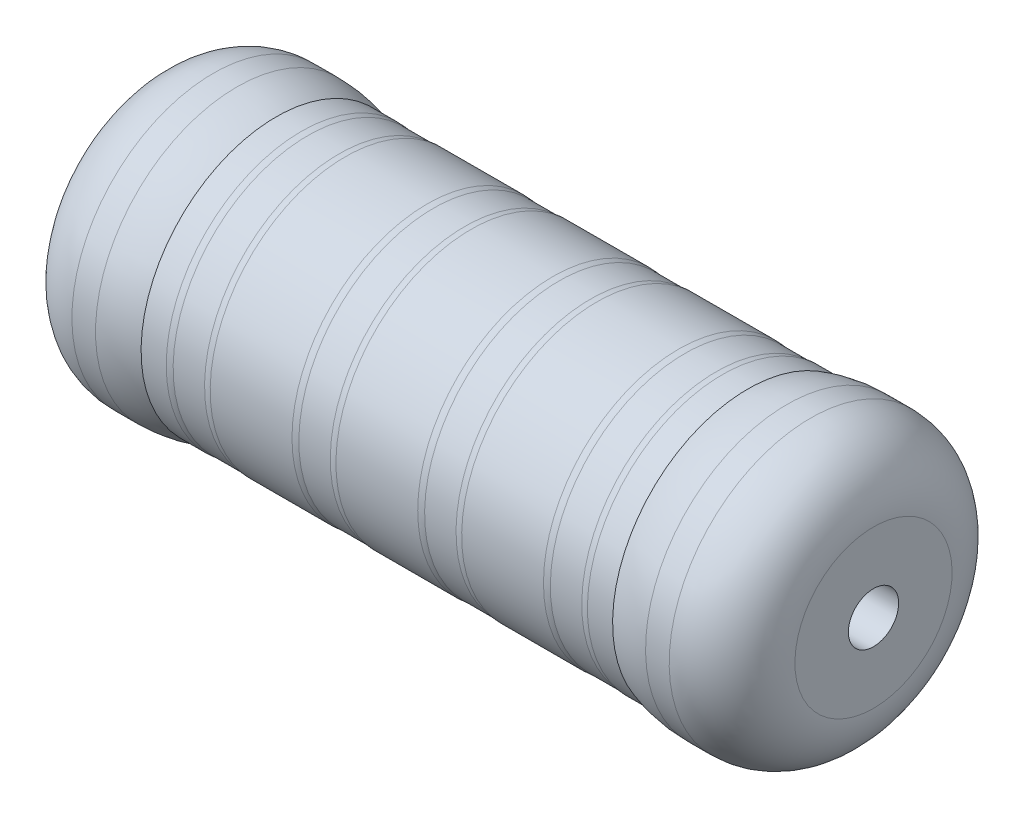
SolidWorks part; units mm, degrees
ref_plane "Front Plane" through (0, 0, 0) normal (0, 0, 1) x (1, 0, 0)
ref_plane "Top Plane" through (0, 0, 0) normal (0, 1, 0) x (1, 0, 0)
ref_plane "Right Plane" through (0, 0, 0) normal (1, 0, 0) x (0, 0, -1)
sketch "Sketch2" plane through (0, 0, 0) normal (0, 0, 1) x (1, 0, 0)
  line L0 (-6.5581, 0) -> (4.9419, 0) construction
  line L1 (-6.5581, 0) -> (-6.5581, 2.25)
  line L2 (4.9419, 0) -> (4.9419, 2.25)
  line L3 (-6.5581, 2.25) -> (-4.5581, 2.25)
  line L4 (-4.5581, 2.25) -> (-4.5581, 2.15)
  line L5 (1.4421, 2.15) -> (2.9419, 2.15)
  line L6 (2.9419, 2.15) -> (2.9419, 2.25)
  line L7 (2.9419, 2.25) -> (4.9419, 2.25)
  line L8 (-4.0581, 2.15) -> (-4.0581, 2.14)
  line L9 (-4.0581, 2.14) -> (-3.5581, 2.14)
  line L10 (-3.5581, 2.14) -> (-3.5581, 2.15)
  line L11 (-3.5581, 2.15) -> (-2.0581, 2.15)
  line L12 (-2.0581, 2.15) -> (-2.0581, 2.14)
  line L13 (-2.0581, 2.14) -> (-1.5581, 2.14)
  line L14 (-1.5581, 2.14) -> (-1.5581, 2.15)
  line L15 (-1.5581, 2.15) -> (-0.0581, 2.15)
  line L16 (-0.0581, 2.15) -> (-0.0581, 2.14)
  line L17 (-0.0581, 2.14) -> (0.4419, 2.14)
  line L18 (0.4419, 2.14) -> (0.4419, 2.15)
  line L19 (0.4419, 2.15) -> (1.9419, 2.15)
  line L20 (1.9419, 2.15) -> (1.9419, 2.14)
  line L21 (1.9419, 2.14) -> (2.4419, 2.14)
  line L22 (2.4419, 2.14) -> (2.4419, 2.15)
  line L23 (-4.5581, 2.15) -> (-4.0581, 2.15)
  line L24 (2.4419, 2.15) -> (2.9419, 2.15)
  point P11 (0, 0)
  point P26 (2.9553, 2.15)
  point P27 (0, 0)
  point P28 (0, 0)
  dimension "D1" = 2.25
  dimension "D2" = 2.25
  dimension "D3" = 11.5
  dimension "D4" = 2
  dimension "D5" = 2
  dimension "D6" = 0.1
  dimension "D7" = 11.5
  dimension "D8" = 0.01
  dimension "D9" = 0.5
  dimension "D10" = 0.01
  dimension "D11" = 1.5
  dimension "D12" = 0.5
  dimension "D13" = 0.01
  dimension "D14" = 0.5
  dimension "D15" = 1.5
  dimension "D16" = 0.01
  dimension "D17" = 1.5
  dimension "D18" = 0.5
  dimension "D19" = 0.5
revolve "Revolve1" add sketch "Sketch2" angle 360 about L0
fillet "Fillet2" radius 1 2 edges at (4.9419, -2.25, 0) (-6.5581, -2.25, 0)
fillet "Fillet10" radius 0.5 8 edges at (-4.0581, -2.15, 0) (-3.5581, -2.15, 0) (-2.0581, -2.15, 0) (-1.5581, -2.15, 0) (-0.0581, -2.15, 0) (0.4419, -2.15, 0) (1.9419, -2.15, 0) (2.4419, -2.15, 0)
fillet "Fillet11" radius 2 2 edges at (2.9419, -2.25, 0) (-4.5581, -2.25, 0)
sketch "Sketch3" plane through (-6.5581, 0, 0) normal (-1, 0, 0) x (0, 0, 1)
  circle A0 centre (0, 0) radius 0.4
  dimension "D1" = 0.8
extrude "Cut-Extrude2" cut sketch "Sketch3" against normal blind 16 contours A0
